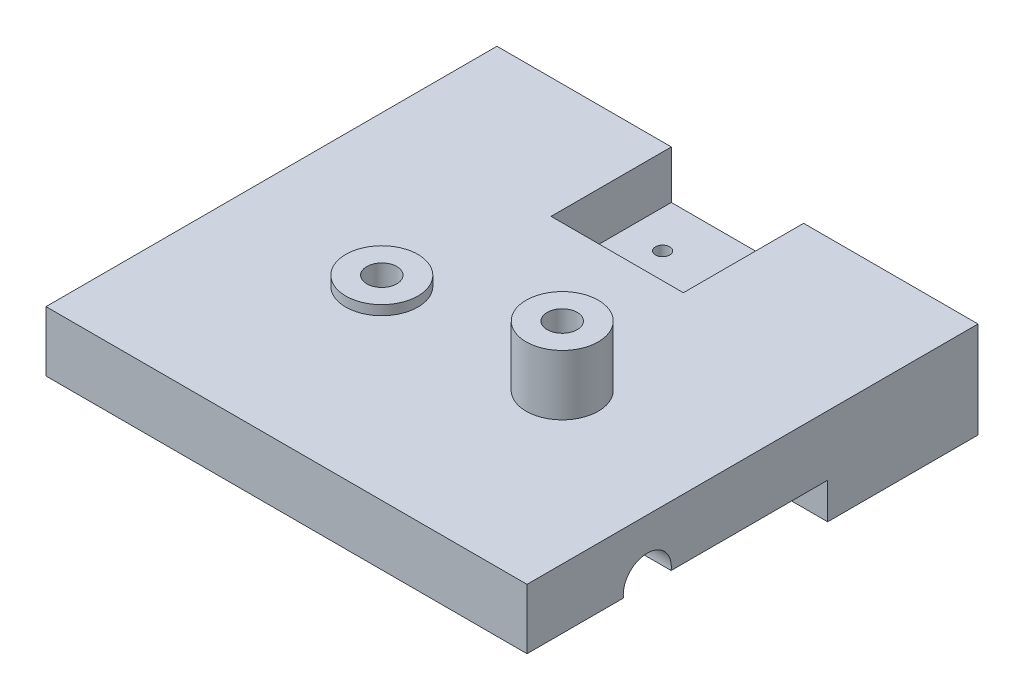
SolidWorks part; units mm, degrees
ref_plane "Front Plane" through (0, 0, 0) normal (0, 0, 1) x (1, 0, 0)
ref_plane "Top Plane" through (0, 0, 0) normal (0, 1, 0) x (1, 0, 0)
ref_plane "Right Plane" through (0, 0, 0) normal (1, 0, 0) x (0, 0, -1)
sketch "Sketch1" plane through (0, 0, 0) normal (0, 1, 0) x (1, 0, 0)
  line L1 (0, 0) -> (80, 0)
  line L2 (0, 0) -> (0, -50)
  line L3 (0, -50) -> (80, -50)
  line L4 (80, 0) -> (80, -50)
  dimension "D1" = 80
  dimension "D2" = 50
extrude "Boss-Extrude1" add sketch "Sketch1" along normal blind 10
sketch "Sketch2" plane through (0, 0, 0) normal (0, 0, 1) x (1, 0, 0)
  line L0 (0, 0) -> (80, 0) construction
  circle A0 centre (14, 0) radius 6.5
  circle A1 centre (66, 0) radius 6.5
  dimension "D1" = 13
  dimension "D2" = 13
  dimension "D3" = 14
  dimension "D4" = 14
extrude "Boss-Extrude3" add sketch "Sketch2" along normal blind 10
sketch "Sketch3" plane through (0, 0, 0) normal (0, 0, -1) x (-1, 0, 0)
  circle A0 centre (-66, 0) radius 6.5
  circle A1 centre (-14, 0) radius 6.5
extrude "Boss-Extrude4" add sketch "Sketch3" along normal blind 15
sketch "Sketch4" plane through (0, 0, -15) normal (0, 0, -1) x (-1, 0, 0)
  circle A0 centre (-14, 0) radius 3.15
  circle A1 centre (-66, 0) radius 3.15
  dimension "D1" = 6.3
  dimension "D2" = 6.3
extrude "Cut-Extrude1" cut sketch "Sketch4" against normal blind 40
sketch "Sketch5" plane through (0, 0, 0) normal (0, -1, 0) x (1, 0, 0)
  line L0 (59.5, 0) -> (20.5, 0) construction
  line L1 (0, 0) -> (0, 50) construction
  line L2 (80, 50) -> (80, 0) construction
  circle A0 centre (25, 14) radius 2.5
  circle A1 centre (55, 14) radius 2.5
  dimension "D1" = 5
  dimension "D2" = 5
  dimension "D3" = 14
  dimension "D4" = 14
  dimension "D5" = 25
  dimension "D6" = 25
ref_plane "Plane1" through (40, 0, 0) normal (-1, 0, 0) x (0, 0, 1)
sketch "Sketch6" plane through (40, 0, 0) normal (-1, 0, 0) x (0, 0, 1)
  line L0 (40, 0) -> (50, 0) construction
  line L1 (0, 0) -> (50, 0) construction
  line L2 (0, 10) -> (50, 10) construction
  line L4 (40, 10) -> (40, 0) construction
  line L5 (50, 10) -> (50, 0) construction
  line L6 (40, 0.5) -> (50, 0.5) construction
  circle A0 centre (40, 0.5) radius 6
  dimension "D3" = 12
  dimension "D1" = 10
  dimension "D2" = 0.5
extrude "Cut-Extrude3" cut sketch "Sketch6" against normal mid plane 19.5 from offset 0 contours A0
sketch "Sketch14" plane through (40, 0, 0) normal (-1, 0, 0) x (0, 0, 1)
  line L0 (10, 0) -> (56.655, 0) construction
  line L1 (50, 10) -> (50, 0) construction
  line L2 (40, 0.5) -> (55.4631, 0.5) construction
  circle A1 centre (40, 0.5) radius 4
  dimension "D1" = 8
  dimension "D2" = 10
  dimension "D3" = 0.5
extrude "Cut-Extrude4" cut sketch "Sketch14" against normal through all both and the other way through all
sketch "Sketch15" plane through (0, 0, 0) normal (0, 0, -1) x (-1, 0, 0)
  line L0 (-28.4, 10) -> (-28.4, 0) construction
  line L5 (0, 10) -> (0, 0) construction
  line L6 (-51.6, 10) -> (-51.6, 0) construction
  line L8 (-80, 10) -> (-80, 0) construction
  line L9 (-59.5, 0) -> (-20.5, 0) construction
  line L10 (-80, 10) -> (0, 10) construction
  line L11 (-51.6, 5) -> (-28.4, 5) construction
  line L12 (-51.6, 10) -> (-28.4, 10)
  line L13 (-51.6, 10) -> (-51.6, 0)
  line L14 (-51.6, 0) -> (-28.4, 0)
  line L15 (-28.4, 10) -> (-28.4, 0)
  line L16 (-50.1, 8.4) -> (-29.9, 8.4)
  line L17 (-50.1, 8.4) -> (-50.1, 1.6)
  line L18 (-50.1, 1.6) -> (-29.9, 1.6)
  line L19 (-29.9, 8.4) -> (-29.9, 1.6)
  dimension "D1" = 28.4
  dimension "D2" = 28.4
  dimension "D3" = 1.6
  dimension "D4" = 1.6
  dimension "D5" = 1.5
  dimension "D6" = 1.5
extrude "Boss-Extrude5" add sketch "Sketch15" along normal blind 15
sketch "Sketch18" plane through (0, 0, 0) normal (-1, 0, 0) x (0, 0, 1)
  line L1 (50, 10) -> (60, 10)
  line L2 (50, 10) -> (50, 0)
  line L3 (50, 0) -> (60, 0)
  line L4 (60, 10) -> (60, 0)
  dimension "D1" = 10
  dimension "D2" = 10
extrude "Boss-Extrude6" add sketch "Sketch18" against normal blind 80
sketch "Sketch19" plane through (0, 0, 0) normal (-1, 0, 0) x (0, 0, 1)
  line L6 (60, 10) -> (36.8, 10)
  line L7 (0, 10) -> (60, 10) construction
  line L8 (36.8, 10) -> (36.8, 0)
  line L9 (43.9686, 0) -> (60, 0) construction
  line L10 (36.8, 0) -> (60, 0)
  line L11 (60, 0) -> (60, 10)
  line L12 (48.4, 10) -> (48.4, 0) construction
  line L13 (36.8, 5) -> (60, 5) construction
  line L15 (38.3, 8.4) -> (58.5, 8.4)
  line L16 (38.3, 8.4) -> (38.3, 1.6)
  line L17 (38.3, 1.6) -> (58.5, 1.6)
  line L18 (58.5, 8.4) -> (58.5, 1.6)
  line L19 (38.3, 8.4) -> (58.5, 1.6) construction
  line L20 (38.3, 1.6) -> (58.5, 8.4) construction
  point P14 (48.4, 5)
  dimension "D1" = 23.2
  dimension "D2" = 20.2
  dimension "D3" = 6.8
sketch "Sketch21" plane through (0, 0, 0) normal (0, 0, -1) x (-1, 0, 0)
  line L1 (-28.4, 10) -> (0, 10)
  line L2 (-28.4, 10) -> (-28.4, -6.5346)
  line L3 (-28.4, -6.5346) -> (0, -6.5346)
  line L4 (0, 10) -> (0, -6.5346)
  circle A1 centre (-14, 0) radius 6.5
  dimension "D3" = 13
  dimension "D1" = 16.5346
  dimension "D2" = 28.4
extrude "Boss-Extrude8" add sketch "Sketch21" along normal blind 15
sketch "Sketch22" plane through (0, 0, 0) normal (0, 0, 1) x (1, 0, 0)
  line L0 (0, 0) -> (7.5, 0)
  line L1 (0, 0) -> (0, -6.5346)
  line L2 (0, -6.5346) -> (28.4, -6.5346)
  line L3 (28.4, -6.5346) -> (28.4, 0)
  line L4 (28.4, 0) -> (20.5, 0)
  arc A0 (7.5, 0) -> (20.5, 0) centre (14, 0) ccw
extrude "Boss-Extrude9" add sketch "Sketch22" along normal blind 10
sketch "Sketch23" plane through (0, 0, 0) normal (0, 0, -1) x (-1, 0, 0)
  line L0 (-80, 10) -> (-51.6, 10)
  line L1 (-51.6, 10) -> (-51.6, -6.5)
  line L2 (-51.6, -6.5) -> (-80, -6.5)
  line L3 (-80, -6.5) -> (-80, 10)
  circle A1 centre (-66, 0) radius 3.15
extrude "Boss-Extrude12" add sketch "Sketch23" along normal blind 15
sketch "Sketch24" plane through (0, 0, 0) normal (0, 0, 1) x (1, 0, 0)
  line L1 (51.6, 0) -> (59.5, 0)
  line L2 (51.6, 0) -> (51.6, -6.5)
  line L3 (51.6, -6.5) -> (80, -6.5)
  line L4 (80, -6.5) -> (80, 0)
  line L5 (80, 0) -> (72.5, 0)
  arc A0 (59.5, 0) -> (72.5, 0) centre (66, 0) ccw
  line M1 (80, 0) -> (72.5, 0)
  arc M2 (72.5, 0) -> (66, -6.5) centre (66, 0) cw
  line M3 (66, -6.5) -> (80, -6.5)
  line M4 (80, -6.5) -> (80, 0)
extrude "Boss-Extrude13" add sketch "Sketch24" along normal blind 10 contours M4 M1 M2 M3 | A0 L1 L2 L3 region at (75.4342, -3.532, 0) region at (56.3607, -3.5198, 0)
sketch "Sketch25" plane through (0, 0, 0) normal (0, -1, 0) x (1, 0, 0)
  line L0 (28.4, 10) -> (51.6, 10)
  line L1 (28.4, 10) -> (28.4, -15)
  line L2 (28.4, -15) -> (51.6, -15)
  line L3 (51.6, -15) -> (51.6, 10)
sketch "Sketch26" plane through (0, 0, 0) normal (0, 0, -1) x (-1, 0, 0)
  line L1 (-50.1, 8.4) -> (-29.9, 8.4)
  line L2 (-50.1, 8.4) -> (-50.1, 1.6)
  line L3 (-50.1, 1.6) -> (-29.9, 1.6)
  line L4 (-29.9, 8.4) -> (-29.9, 1.6)
extrude "Boss-Extrude15" add sketch "Sketch26" along normal blind 15
sketch "Sketch27" plane through (0, 0, -15) normal (0, 0, -1) x (-1, 0, 0)
  line L0 (-51, 10) -> (-40, 10)
  line L1 (-40, 10) -> (-40, 2) construction
  line L2 (-40, 10) -> (-29, 10)
  line L3 (-51, 10) -> (-51, 2)
  line L5 (-51, 2) -> (-29, 2)
  line L6 (0, 10) -> (-80, 10) construction
  line L14 (-29, 2) -> (-29, 10)
  line L15 (-40, 1.7414) -> (-40, 1.735) construction
  point P12 (-40, 1.735)
  dimension "D1" = 11
  dimension "D2" = 11
  dimension "D3" = 8
extrude "Cut-Extrude7" cut sketch "Sketch27" against normal blind 20
sketch "Sketch30" plane through (0, 2, 0) normal (0, 1, 0) x (1, 0, 0)
  line L0 (40, -5) -> (40, 15) construction
  line L1 (29, -5) -> (51, -5) construction
  line L2 (51, 15) -> (29, 15) construction
  line L3 (45, -5) -> (40, -5)
  line L6 (40, -1) -> (45, -1)
  line L7 (45, -1) -> (45, -5)
  line L8 (40, -5) -> (35, -5)
  line L9 (51, -5) -> (29, -5) construction
  line L10 (35, -5) -> (35, -1)
  line L11 (35, -1) -> (40, -1)
  dimension "D1" = 5
  dimension "D2" = 5
  dimension "D3" = 4
extrude "Cut-Extrude8" cut sketch "Sketch30" against normal blind 16
sketch "Sketch32" plane through (80, 0, 0) normal (1, 0, 0) x (0, 0, -1)
  line L0 (15, 10) -> (15, -6.5) construction
  line L3 (-60, -6) -> (15, -6)
  line L5 (15, -6) -> (15, -8.556)
  line L6 (15, -8.556) -> (-60, -8.556)
  line L7 (-60, -8.556) -> (-60, -6)
extrude "Cut-Extrude9" cut sketch "Sketch32" against normal blind 116.53
sketch "Sketch38" plane through (0, 2, 0) normal (0, 1, 0) x (1, 0, 0)
  line L0 (51, 15) -> (29, 15) construction
  line L3 (40, 15) -> (40, -1) construction
  line L4 (45, -1) -> (35, -1) construction
  circle A0 centre (35.25, 7.3) radius 1.185
  circle A1 centre (44.75, 7.3) radius 1.185
  dimension "D4" = 2.37
  dimension "D5" = 7.7
  dimension "D1" = 7.7
  dimension "D2" = 4.75
  dimension "D3" = 4.75
extrude "Cut-Extrude12" cut sketch "Sketch38" against normal blind 20
sketch "Sketch39" plane through (0, -6, 0) normal (0, -1, 0) x (1, 0, 0)
  line L0 (28.4, 10) -> (51.6, 10)
  line L1 (51.6, 10) -> (51.6, -15)
  line L2 (51.6, -15) -> (28.4, -15)
  line L3 (28.4, -15) -> (28.4, 10)
  line L4 (35, 5) -> (45, 5)
  line L5 (45, 5) -> (45, 1)
  line L6 (45, 1) -> (35, 1)
  line L7 (35, 1) -> (35, 5)
  circle A0 centre (35.25, -7.3) radius 1.185
  circle A1 centre (44.75, -7.3) radius 1.185
extrude "Boss-Extrude18" add sketch "Sketch39" against normal blind 6
sketch "Sketch40" plane through (0, 10, 0) normal (0, 1, 0) x (1, 0, 0)
  line L0 (25, -29.15) -> (55, -29.15) construction
  line L3 (0, 15) -> (29, 15) construction
  circle A0 centre (25, -29.15) radius 2.5
  circle A1 centre (55, -29.15) radius 2.5
  point P6 (74.5328, 18.1015)
  dimension "D1" = 5
  dimension "D2" = 5
  dimension "D3" = 44.15
  dimension "D5" = 30
extrude "Cut-Extrude13" cut sketch "Sketch40" against normal blind 20
extrude "Cut-Extrude14" cut sketch "Sketch5" against normal blind 77.25
sketch "Sketch42" plane through (0, 10, 0) normal (0, 1, 0) x (1, 0, 0)
  circle A0 centre (55, -29.15) radius 2.5
  circle A1 centre (55, -29.15) radius 6
  dimension "D1" = 12
extrude "Boss-Extrude20" add sketch "Sketch42" along normal blind 10
sketch "Sketch43" plane through (0, 10, 0) normal (0, 1, 0) x (1, 0, 0)
  circle A0 centre (25, -29.15) radius 2.5
  circle A1 centre (25, -29.15) radius 6
  dimension "D1" = 12
extrude "Boss-Extrude21" add sketch "Sketch43" along normal blind 1.6
sketch "Sketch44" plane through (0, 10, 0) normal (0, 1, 0) x (1, 0, 0)
  circle A0 centre (25, -14) radius 2.5
  circle A1 centre (55, -14) radius 2.5
extrude "Boss-Extrude22" add sketch "Sketch44" against normal blind 10
sketch "Sketch45" plane through (0, 0, 0) normal (-1, 0, 0) x (0, 0, 1)
  text T0 "29"
extrude "Cut-Extrude15" cut sketch "Sketch45" against normal blind 2
